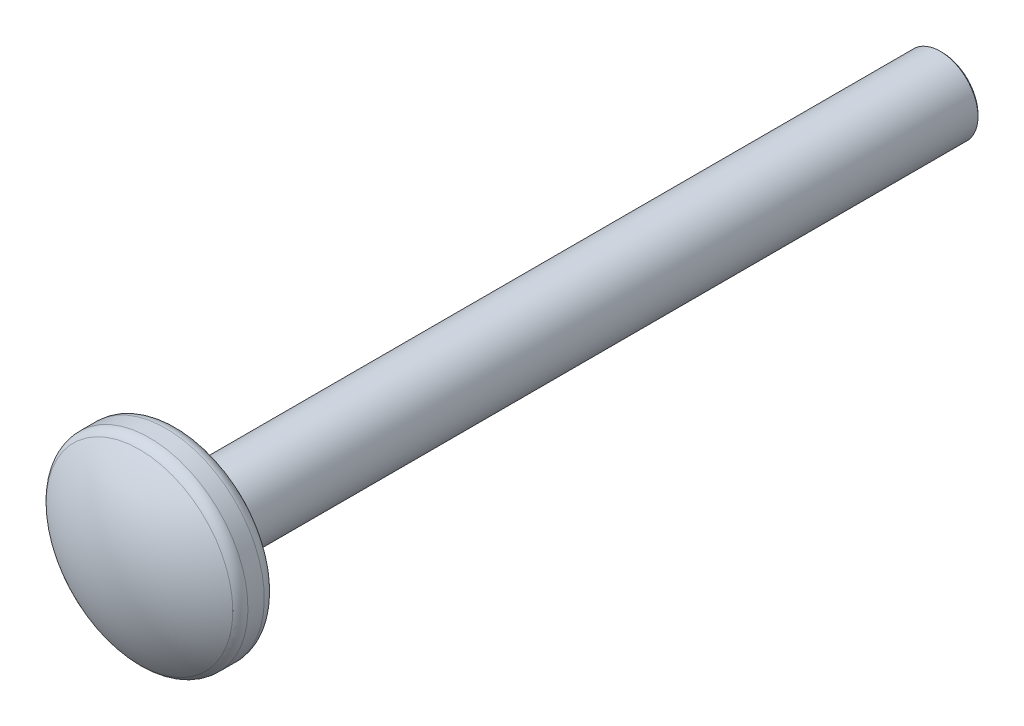
SolidWorks part; units mm, degrees
material "AISI 304"
ref_plane "Front Plane" through (0, 0, 0) normal (0, 0, 1) x (1, 0, 0)
ref_plane "Top Plane" through (0, 0, 0) normal (0, 1, 0) x (1, 0, 0)
ref_plane "Right Plane" through (0, 0, 0) normal (1, 0, 0) x (0, 0, -1)
sketch "Sketch1" plane through (0, 0, 0) normal (0, 0, 1) x (1, 0, 0)
  circle A0 centre (0, 0) radius 2.0828
  dimension "decimal equ" = 4.1656
curve "Helix/Spiral1" pitch 0.7937 height 32.5437 turns 41 parameters "helix length"=32.5437, "pitch"=0.7937
sketch "Sketch2" plane through (0, 0, 0) normal (1, 0, 0) x (0, 0, -1)
  line L0 (0.2977, 2.0828) -> (0.3969, 2.0828)
  line L1 (0.3969, 2.0828) -> (0.6945, 1.5672)
  line L2 (0.2977, 2.0828) -> (0, 1.5672)
  line L3 (0, 1.5672) -> (0.6945, 1.5672)
  line L4 (0.3473, 2.0828) -> (0.3473, 1.5672) construction
  line L6 (0.1488, 1.825) -> (0.5457, 1.825) construction
  line L7 (0, 1.5672) -> (0, 2.0828) construction
  line L8 (0, 2.0828) -> (0, -2.0828) construction
  line L9 (0, 2.0828) -> (0, -2.0828) construction
  point P8 (-3.2742, -2.0828)
  dimension "D1" = 60
  dimension "D3" = 0.0992
  dimension "D4" = 0.3969
  dimension "D2" = 3.2742
sketch "Sketch3" plane through (0, 0, 0) normal (1, 0, 0) x (0, 0, -1)
  line L0 (0, 0) -> (-31.75, 0) construction
  line L1 (0, 1.5672) -> (0.6945, 1.5672) construction
  line L2 (0, 0) -> (-31.75, 0)
  line L3 (0, 0) -> (0, 1.5672)
  line L4 (0, 1.5672) -> (-31.75, 1.5672)
  line L5 (-31.75, 0) -> (-31.75, 1.5672)
  dimension "length" = 31.75
revolve "Revolve1" add sketch "Sketch3" angle 360 about L0
sweep "Sweep1" [suppressed] add profiles "Sketch2" path "Helix/Spiral1"
sketch "Sketch39" plane through (0, 0, 0) normal (0, 0, -1) x (-1, 0, 0)
  circle A0 centre (0, 0) radius 2.0828 construction
  circle A1 centre (0, 0) radius 2.0828
extrude "Extrude5" [suppressed] cut sketch "Sketch39" along normal through all
sketch "Sketch38" plane through (0, 0, 0) normal (0, 0, -1) x (-1, 0, 0)
  circle A2 centre (0, 0) radius 1.4875
  circle A3 centre (0, 0) radius 1.4875
extrude "Extrude6" cut sketch "Sketch38" against normal through all draft 45 flip side to cut
sketch "Sketch10" plane through (0, 0, 0) normal (1, 0, 0) x (0, 0, -1)
  line L0 (0, 0) -> (23.0169, 0) construction
  line L1 (-285.75, 12.7) -> (-31.75, 12.7)
  line L2 (-285.75, 12.7) -> (-285.75, 0)
  line L3 (-285.75, 0) -> (-31.75, 0)
  line L4 (-31.75, 12.7) -> (-31.75, 0)
  line L5 (-31.75, 0) -> (-31.75, 1.5672) construction
  dimension "D1" = 254
  dimension "D2" = 12.7
revolve "Cut-Revolve2" [suppressed] cut sketch "Sketch10" angle 360 about L0
sketch "Sketch41" plane through (0, 0, 0) normal (1, 0, 0) x (0, 0, -1)
  line L0 (-31.75, 2.0828) -> (-31.75, 1.5672)
  line L1 (-31.75, 1.5672) -> (-30.8737, 1.5672)
  line L2 (-30.8737, 1.5672) -> (-30.3581, 2.0828)
  line L3 (-31.75, 2.0828) -> (-30.3581, 2.0828)
  line L4 (0, 1.5672) -> (0.6945, 1.5672) construction
  dimension "D1" = 0.8763
  dimension "D2" = 45
revolve "Cut-Revolve4" [suppressed] cut sketch "Sketch41" angle 360 about L2
sketch "Sketch8" plane through (0, 0, 0) normal (1, 0, 0) x (0, 0, -1)
  line L0 (0, 0) -> (-6.2449, 0) construction
  line L1 (-34.671, 0) -> (-31.75, 0)
  line L2 (-34.671, 0) -> (-34.671, 4.0894)
  line L3 (-34.671, 4.0894) -> (-31.75, 4.0894)
  line L4 (-31.75, 0) -> (-31.75, 4.0894)
  line L5 (-34.671, -4.0894) -> (-31.75, -4.0894) construction
  line L6 (-31.75, 0) -> (-31.75, 1.5672) construction
  dimension "head dia" = 8.1788
  dimension "head height" = 2.921
revolve "Revolve2" add sketch "Sketch8" angle 360 about L0
sketch "Sketch11" plane through (0, 0, 0) normal (1, 0, 0) x (0, 0, -1)
  line L0 (-33.2105, 4.0894) -> (-33.2105, -4.0894) construction
  line L1 (-34.671, 0) -> (-6.8951, 0) construction
  line L2 (-34.671, 4.0894) -> (-31.75, 4.0894) construction
  line L3 (-34.671, 0) -> (-34.671, 4.0894) construction
  line L4 (-32.9549, 4.0894) -> (-32.2758, 4.0894)
  line L6 (-31.75, 0) -> (-31.75, 4.0894) construction
  line L7 (-31.75, 3.5636) -> (-31.115, 3.5636)
  line L8 (-31.115, 3.5636) -> (-31.115, 4.7244)
  line L9 (-31.115, 4.7244) -> (-35.306, 4.7244)
  line L10 (-35.306, 4.7244) -> (-35.306, 0)
  line L11 (-35.306, 0) -> (-34.671, 0)
  arc A0 (-33.3751, 3.8796) -> (-34.671, 0) centre (-28.2156, 0) ccw
  arc A1 (-31.75, 3.5636) -> (-32.2758, 4.0894) centre (-32.2758, 3.5636) ccw
  arc A2 (-33.3751, 3.8796) -> (-32.9549, 4.0894) centre (-32.9549, 3.5636) cw
  dimension "D1" = 0.5258
  dimension "D2" = 0.635
  dimension "D3" = 0.635
  dimension "D4" = 0.635
revolve "Cut-Revolve3" cut sketch "Sketch11" angle 360 about L1
ref_plane "Plane1" through (0, 0, 34.671) normal (0, 0, 1) x (1, 0, 0)
sketch "Sketch12" plane through (0, 0, 34.671) normal (0, 0, 1) x (1, 0, 0)
  line L0 (0.508, 2.3264) -> (0.508, 1.1906)
  line L1 (0.508, 1.1906) -> (1.1906, 0.508) construction
  line L2 (1.1906, 0.508) -> (2.3264, 0.508)
  line L3 (0, 2.3813) -> (0, 0)
  line L4 (0, 0) -> (2.3813, 0)
  line L5 (0, 0) -> (0, 4.0894) construction
  line L6 (0, 0) -> (0.8493, 0.8493) construction
  line L7 (1.1906, 0) -> (1.1906, 1.5633) construction
  line L8 (0.508, 1.1906) -> (0.7079, 0.7079)
  line L9 (1.1906, 0.508) -> (0.7079, 0.7079)
  line L10 (0, 0) -> (0, -1.0114) construction
  line L11 (-0.508, 2.3264) -> (-0.508, 1.1906) construction
  arc A0 (2.3813, 0) -> (2.3264, 0.508) centre (0, 0) ccw
  arc A1 (0.508, 2.3264) -> (0, 2.3813) centre (0, 0) ccw
  arc A2 (-2.3813, 0) -> (-2.3264, 0.508) centre (0, 0) cw construction
  dimension "phillips dia" = 4.7625
  dimension "D2" = 45
  dimension "D4" = 22.5
  dimension "slot width" = 1.016
extrude "Cut-Extrude1" [suppressed] cut sketch "Sketch12" against normal blind 2.4829
draft "Draft3" [suppressed] type of draft neutral plane draft angle 15 neutral plane "Plane1" faces to draft 2 parameters "D1"=15
draft "Draft4" [suppressed] type of draft neutral plane draft angle 5 neutral plane "Plane1" faces to draft 4 parameters "D1"=5
pattern_circular "CirPattern1" [suppressed] count 4 over 360 about axis through (0, 0, 34.671) along (0, 0, -1) of bodies 110
ref_plane "Plane8" through (0, 0, 31.5939) normal (0, 0, -1) x (-1, 0, 0)
sketch "Sketch18" plane through (0, 0, 31.5939) normal (0, 0, 1) x (1, 0, 0)
  line L0 (0, 0) -> (0, 4.064) construction
  line L1 (1.5672, 0) -> (4.064, 0) construction
  circle A0 centre (0, 0) radius 4.064
  circle A1 centre (0, 0) radius 1.5672 construction
  circle A2 centre (0, 0) radius 1.5672 construction
  circle A3 centre (0, 0) radius 2.6908
  circle A4 centre (0, 0) radius 2.0828 construction
  point P8 (2.6908, 0)
  point P10 (0, 2.6908)
  dimension "washer dia." = 8.128
  dimension "D2" = 1.1235
sketch "Sketch21" plane through (0, 0, 31.5939) normal (0, 0, 1) x (1, 0, 0)
  circle A0 centre (0, 0) radius 2.6908
  circle A1 centre (0, 0) radius 1.5672
  circle A2 centre (0, 0) radius 2.0828 construction
extrude "Extrude2" add sketch "Sketch21" against normal blind 0.5842 separate body
ref_plane "Plane9" through (0, 2.6908, 0) normal (0, 1, 0) x (-1, 0, 0)
sketch "Sketch31" plane through (0, 2.6908, 0) normal (0, 1, 0) x (-1, 0, 0)
  line L1 (-0.508, 31.5939) -> (0.508, 31.5939)
  line L2 (-0.508, 31.5939) -> (-0.508, 31.0097)
  line L3 (-0.508, 31.0097) -> (0.508, 31.0097)
  line L4 (0.508, 31.5939) -> (0.508, 31.0097)
  line L5 (-2.6908, 31.0097) -> (2.6908, 31.0097) construction
  line L6 (0, 0) -> (0, 31.5939) construction
  line L7 (0.508, 31.3018) -> (-0.508, 31.3018) construction
  line L8 (0, 31.5939) -> (0, 31.0097) construction
  line L9 (2.6908, 31.5939) -> (-2.6908, 31.5939) construction
  dimension "D1" = 1.016
ref_plane "Plane10" through (0, 4.064, 0) normal (0, 1, 0) x (-1, 0, 0)
sketch "Sketch32" plane through (0, 4.064, 0) normal (0, 1, 0) x (-1, 0, 0)
  line L0 (-0.3775, 31.75) -> (-0.5773, 31.201)
  line L1 (-0.3775, 31.75) -> (0.5773, 31.4025)
  line L2 (-0.5773, 31.201) -> (0.3775, 30.8535)
  line L3 (0.5773, 31.4025) -> (0.3775, 30.8535)
  line L4 (-0.508, 31.5939) -> (-0.508, 31.0097) construction
  line L5 (-0.508, 31.0097) -> (0.508, 31.0097) construction
  line L6 (0.0999, 31.5763) -> (0, 31.3018) construction
  line L7 (0, 31.3018) -> (0.4774, 31.128) construction
  line L8 (0.508, 31.3018) -> (-0.508, 31.3018) construction
  line L9 (0, 0) -> (0, 6.2449) construction
  line L10 (-1.5672, 31.0097) -> (1.5672, 31.0097) construction
  dimension "D1" = 20
sketch "Sketch33" plane through (0, 2.6908, 0) normal (0, 1, 0) x (-1, 0, 0)
  line L1 (1.5672, 31.5939) -> (-1.5672, 31.5939) construction
  line L4 (0.508, 31.5939) -> (-0.508, 31.5939)
  line L5 (0.508, 31.0097) -> (0.508, 31.5939)
  line L6 (-0.508, 31.0097) -> (0.508, 31.0097)
  line L7 (-0.508, 31.5939) -> (-0.508, 31.0097)
  line L8 (0.508, 31.5939) -> (-0.508, 31.5939)
  line L9 (0.508, 31.0097) -> (0.508, 31.5939)
  line L10 (-0.508, 31.0097) -> (0.508, 31.0097)
  line L11 (-0.508, 31.5939) -> (-0.508, 31.0097)
  dimension "D1" = 0
extrude "Extrude3" [suppressed] add sketch "Sketch33" against normal up to next
loft "Loft2" [suppressed] add profiles "Sketch32", "Sketch31"
pattern_circular "CirPattern4" [suppressed] count 12 over 360 of bodies 186
sketch "Sketch40" plane through (0, 0, 0) normal (1, 0, 0) x (0, 0, -1)
  line L0 (-31.5939, 4.064) -> (-31.0097, 4.064) construction
  line L1 (-31.5939, -4.064) -> (-31.0097, -4.064) construction
  line L2 (-31.3018, 4.064) -> (-31.3018, -4.064) construction
  line L3 (-31.3018, 0) -> (0, 0) construction
  line L4 (0, -1.4875) -> (0, 1.4875) construction
  line L6 (-31.5939, -5.9931) -> (-31.5939, 5.9931) construction
  dimension "D1" = 0.5842
  dimension "D2" = 8.128
equation "\"D3@Sketch2\" = \"pitch@Helix/Spiral1\"*.125"
equation "\"D4@Sketch2\" = \"pitch@Helix/Spiral1\"*.5"
equation "\"D1@Sketch11\" = \"head height@Sketch8\"*.18"
equation "\"D1@Cut-Extrude1\" = \"head height@Sketch8\"*.85"
equation "\"D1@Sketch31\" = \"washer dia.@Sketch18\"*.125"
equation "\"helix length@Helix/Spiral1\" = \"length@Sketch3\" + \"pitch@Helix/Spiral1\""
equation "\"D1@Sketch38\" = \"pitch@Helix/Spiral1\"*.750"
equation "\"D1@Plane8\" = \"D2@Sketch32\""
equation "\"D2@Sketch18\" = \"D1@Sketch18\"*.45"
equation "\"D2@Sketch2\" = \"pitch@Helix/Spiral1\"*4.125"
equation "\"D1@Sketch40\" = \"washer width@Extrude2\""
equation "\"D2@Sketch40\" = \"washer dia.@Sketch18\""
equation "\"D1@Sketch41\" = \"washer width@Extrude2\"*1.50"
